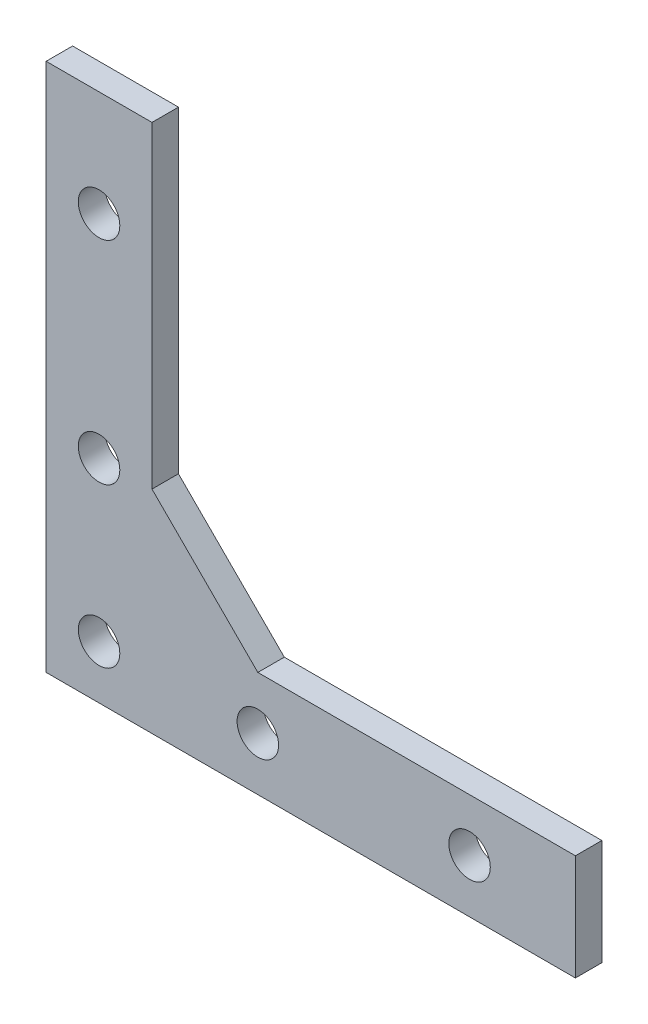
SolidWorks part; units mm, degrees
material "6061 Alloy"
ref_plane "Front Plane" through (0, 0, 0) normal (0, 0, 1) x (1, 0, 0)
ref_plane "Top Plane" through (0, 0, 0) normal (0, 1, 0) x (1, 0, 0)
ref_plane "Right Plane" through (0, 0, 0) normal (1, 0, 0) x (0, 0, -1)
sketch "Sketch1" plane through (0, 0, 0) normal (0, 0, 1) x (1, 0, 0)
  line L0 (-253.5966, 0) -> (-266.7, 0)
  line L1 (-266.7, 0) -> (-266.7, 63.5)
  line L2 (-266.7, 63.5) -> (-254, 63.5)
  line L3 (-254, -16.7024) -> (-254, 609.6) construction
  line L4 (-253.5966, 0) -> (-203.2, 0)
  line L6 (-203.2, 0) -> (-203.2, 12.7)
  line L7 (-254, 12.7) -> (254, 12.7) construction
  line L8 (-203.2, 12.7) -> (-241.3, 12.7)
  line L9 (-241.3, 12.7) -> (-254, 25.4)
  line L10 (-254, 25.4) -> (-254, 63.5)
  point P2 (0, 0)
  point P9 (0, 0)
  dimension "D1" = 63.5
  dimension "D2" = 12.7
  dimension "D3" = 38.1
  dimension "D4" = 12.7
  dimension "D5" = 38.1
  dimension "D6" = 63.5
extrude "Boss-Extrude1" add sketch "Sketch1" along normal blind 3.175
sketch "Sketch2" plane through (0, 0, 3.175) normal (0, 0, 1) x (1, 0, 0)
  line L0 (-260.35, 63.5) -> (-260.35, 50.8382) construction
  line L1 (-254, 63.5) -> (-266.7, 63.5) construction
  line L2 (-260.35, 50.8382) -> (-260.35, 25.4382) construction
  line L3 (-260.35, 6.3882) -> (-241.3, 6.3882) construction
  line L4 (-260.35, 25.4382) -> (-260.35, 6.3882) construction
  line L5 (-241.3, 6.3882) -> (-215.9, 6.3882) construction
  line L6 (-203.2, 6.35) -> (-215.9, 6.3882) construction
  line L7 (-203.2, 0) -> (-203.2, 12.7) construction
  point P9 (0, 0)
  point P12 (0, 0)
  point P14 (0, 0)
  dimension "D1" = 19.05
  dimension "D2" = 19.05
  dimension "D3" = 25.4
  dimension "D4" = 25.4
hole_wizard "#10 Clearance Hole1" positions "Sketch3" profile "Sketch4" hole size "#10" standard "ANSI Inch" end condition through all
sketch "Sketch3" plane through (0, 0, 3.175) normal (0, 0, 1) x (1, 0, 0)
  point P0 (-260.35, 6.3882)
  point P3 (-260.35, 25.4382)
  point P6 (-260.35, 50.8382)
  point P9 (-241.3, 6.3882)
  point P12 (-215.9, 6.3882)
sketch "Sketch4" plane through (-260.35, 6.3882, 3.175) normal (1, 0, 0) x (0, -1, 0)
  line L0 (0, 0) -> (0, 3.175)
  line L1 (0, 3.175) -> (2.4892, 3.175)
  line L2 (2.4892, 3.175) -> (2.4892, 0)
  line L5 (2.4892, 0) -> (0, 0)
  line L11 (0, -6.35) -> (0, 107.95) construction
  dimension "Thru Hole Dia." = 4.9784
  dimension "Thru Hole Depth" = 3.175
